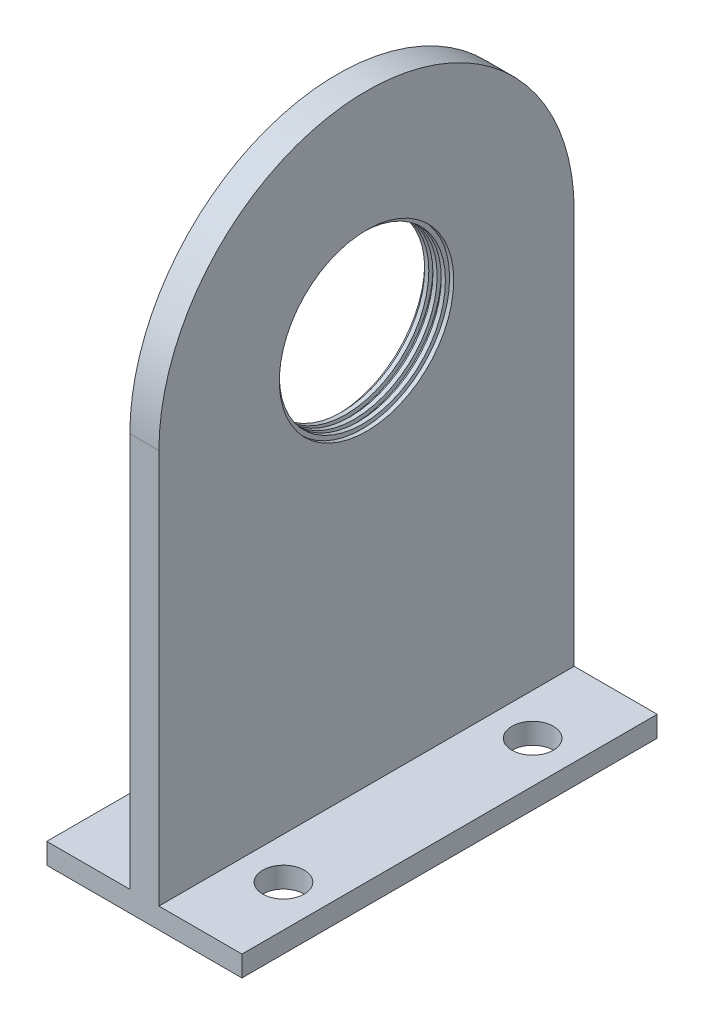
SolidWorks part; units mm, degrees
ref_plane "Front" through (0, 0, 0) normal (0, 0, 1) x (1, 0, 0)
ref_plane "Top" through (0, 0, 0) normal (0, 1, 0) x (1, 0, 0)
ref_plane "Right" through (0, 0, 0) normal (1, 0, 0) x (0, 0, -1)
sketch "Sketch1" plane through (0, 0, 0) normal (1, 0, 0) x (0, 0, -1)
  line L0 (0, 55) -> (0, -55) construction
  line L1 (-5, 0) -> (5, 0)
  line L2 (-5, 0) -> (-5, 10)
  line L4 (5, 0) -> (5, 10)
  line L5 (55, 0) -> (-55, 0) construction
  arc A0 (-5, 10) -> (5, 10) centre (0, 10) cw
  circle A1 centre (0, 10) radius 2
  dimension "D4" = 5
  dimension "D5" = 4
  dimension "D1" = 10
  dimension "D2" = 5
  dimension "D3" = 10
extrude "Boss-Extrude1" add sketch "Sketch1" along normal blind 0.7
ref_plane "Plane1" through (0.1, 0, 0) normal (1, 0, 0) x (0, 0, -1)
ref_plane "Plane2" through (0.3, 0, 0) normal (1, 0, 0) x (0, 0, -1)
ref_plane "Plane3" through (0.5, 0, 0) normal (1, 0, 0) x (0, 0, -1)
ref_plane "Plane4" through (0.7, 0, 0) normal (1, 0, 0) x (0, 0, -1)
sketch "Sketch2" plane through (0, 0, 0) normal (1, 0, 0) x (0, 0, -1)
  circle A0 centre (0, 10) radius 2.1
extrude "Cut-Extrude1" cut sketch "Sketch2" along normal blind 0.1
sketch "Sketch3" plane through (0.7, 0, 0) normal (1, 0, 0) x (0, 0, -1)
  circle A0 centre (0, 10) radius 2.1
  dimension "D1" = 4.2
extrude "Cut-Extrude2" cut sketch "Sketch3" against normal blind 0.1
sketch "Sketch4" plane through (0.5, 0, 0) normal (1, 0, 0) x (0, 0, -1)
  circle A0 centre (0, 10) radius 2.1
extrude "Cut-Extrude3" cut sketch "Sketch4" against normal blind 0.1
sketch "Sketch5" plane through (0.3, 0, 0) normal (1, 0, 0) x (0, 0, -1)
  circle A0 centre (0, 10) radius 2.1
extrude "Cut-Extrude4" cut sketch "Sketch5" against normal blind 0.1
sketch "Sketch6" plane through (0, 0, 0) normal (1, 0, 0) x (0, 0, -1)
  line L1 (-5, 0) -> (5, 0)
  line L2 (-5, 0) -> (-5, 0.5)
  line L3 (-5, 0.5) -> (5, 0.5)
  line L4 (5, 0) -> (5, 0.5)
  dimension "D1" = 0.5
extrude "Boss-Extrude2" add sketch "Sketch6" along normal blind 2.7 and the other way blind 2
sketch "Sketch7" plane through (0, 0.5, 0) normal (0, 1, 0) x (1, 0, 0)
  line L0 (2.7, 5) -> (2.7, -5) construction
  line L3 (-2.585, 0) -> (2.585, 0) construction
  circle A0 centre (1.7, 3) radius 0.5
  circle A1 centre (1.7, -3) radius 0.5
  dimension "D1" = 1
  dimension "D2" = 1
  dimension "D3" = 1
  dimension "D4" = 1
  dimension "D5" = 3
  dimension "D6" = 3
extrude "Cut-Extrude5" cut sketch "Sketch7" against normal blind 2.7
sketch "Sketch8" plane through (0, 0.5, 0) normal (0, 1, 0) x (1, 0, 0)
  line L1 (-2, 5) -> (-2, -5) construction
  line L2 (-2.585, 0) -> (2.585, 0) construction
  circle A0 centre (-1, 3) radius 0.5
  circle A1 centre (-1, -3) radius 0.5
  dimension "D1" = 1
  dimension "D2" = 1
  dimension "D3" = 1
  dimension "D4" = 1
  dimension "D5" = 3
  dimension "D6" = 3
extrude "Cut-Extrude6" cut sketch "Sketch8" against normal blind 2.7
